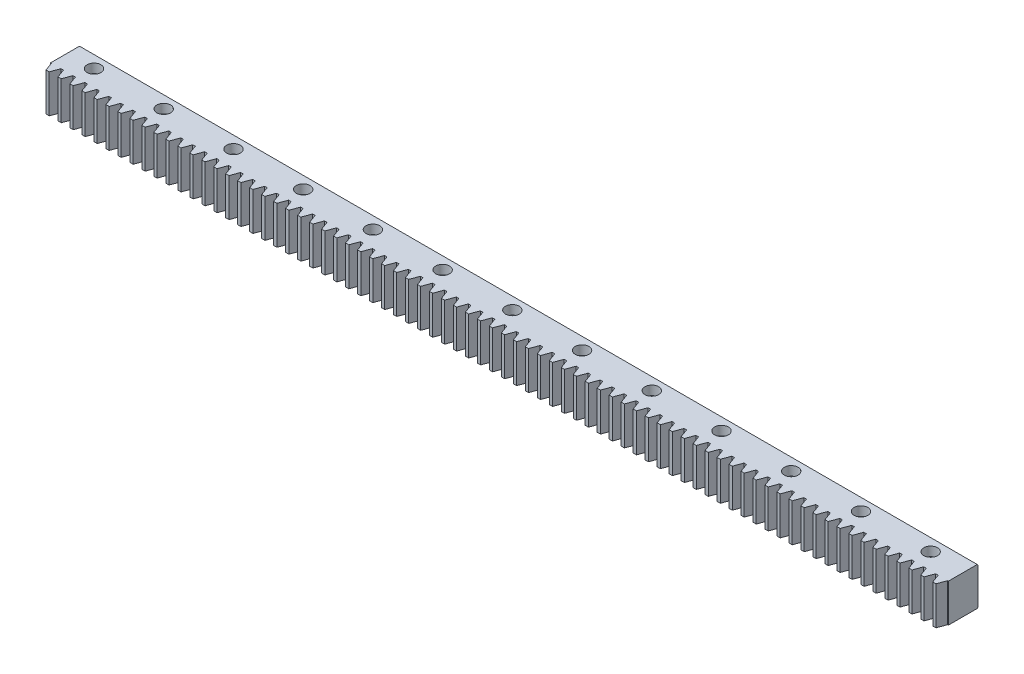
SolidWorks part; units mm, degrees
ref_plane "前基準面" through (0, 0, 0) normal (0, 0, 1) x (1, 0, 0)
ref_plane "上基準面" through (0, 0, 0) normal (0, 1, 0) x (1, 0, 0)
ref_plane "右基準面" through (0, 0, 0) normal (1, 0, 0) x (0, 0, -1)
sketch "草圖1" plane through (0, 0, 0) normal (0, 1, 0) x (1, 0, 0)
  line L1 (-588.395, 0) -> (588.395, 0)
  line L2 (-588.395, 0) -> (-588.395, -50)
  line L3 (-588.395, -50) -> (588.395, -50)
  line L4 (588.395, 0) -> (588.395, -50)
  dimension "D1" = 50
  dimension "D2" = 1176.7901
extrude "伸長1" add sketch "草圖1" along normal mid plane 50
sketch "草圖2" plane through (0, 25, 0) normal (0, 1, 0) x (1, 0, 0)
  line L0 (583.3032, -50) -> (587.3979, -38.75)
  line L1 (-588.395, -50) -> (588.395, -50) construction
  line L2 (587.3979, -38.75) -> (590.7022, -38.75)
  line L3 (590.7022, -38.75) -> (594.7969, -50)
  line L4 (594.7969, -50) -> (583.3032, -50)
  line L6 (585.1231, -45) -> (592.977, -45) construction
  line L8 (589.05, -38.75) -> (589.05, -54.3263) construction
  line L10 (588.395, -50) -> (588.395, 0) construction
  dimension "D1" = 0.655
  dimension "D2" = 40
  dimension "D3" = 5
  dimension "D4" = 11.25
  dimension "D5" = 7.854
extrude "除料-伸長1" cut sketch "草圖2" against normal up to next
pattern_linear "直線複製排列1" count 76 spacing 15.708 along (-1, 0, 0) of "除料-伸長1"
chamfer "導角1" distance 1 angle 45 2 edges at (0, -25, 0) (0, 25, 0)
hole_wizard "M10 六角承窩頭蓋螺釘的柱孔1" positions "草圖6" profile "草圖5" counterbore size "M10" standard "ISO" end condition through all
sketch "草圖6" plane through (0, 25, 0) normal (0, 1, 0) x (-1, 0, 0)
  line L4 (588.395, 0) -> (-588.395, 0) construction
  line L5 (-588.395, 38.75) -> (-588.395, 1) construction
  point P3 (-543.3551, 17)
  dimension "D1" = 17
  dimension "D2" = 45.04
sketch "草圖5" plane through (543.3551, 25, 17) normal (1, 0, 0) x (0, 0, 1)
  line L0 (0, 0) -> (0, 50)
  line L1 (0, 50) -> (5.5, 50)
  line L3 (5.5, 50) -> (5.5, 12)
  line L4 (5.5, 12) -> (9, 12)
  line L5 (9, 12) -> (9, 0)
  line L7 (9, 0) -> (0, 0)
  line L11 (0, -6.35) -> (0, 107.95) construction
  dimension "貫穿孔直徑" = 11
  dimension "貫穿孔深度" = 50
  dimension "柱孔直徑" = 18
  dimension "柱孔深度" = 12
pattern_linear "直線複製排列2" count 13 spacing 91.392 along (-1, 0, 0) of "M10 六角承窩頭蓋螺釘的柱孔1"
